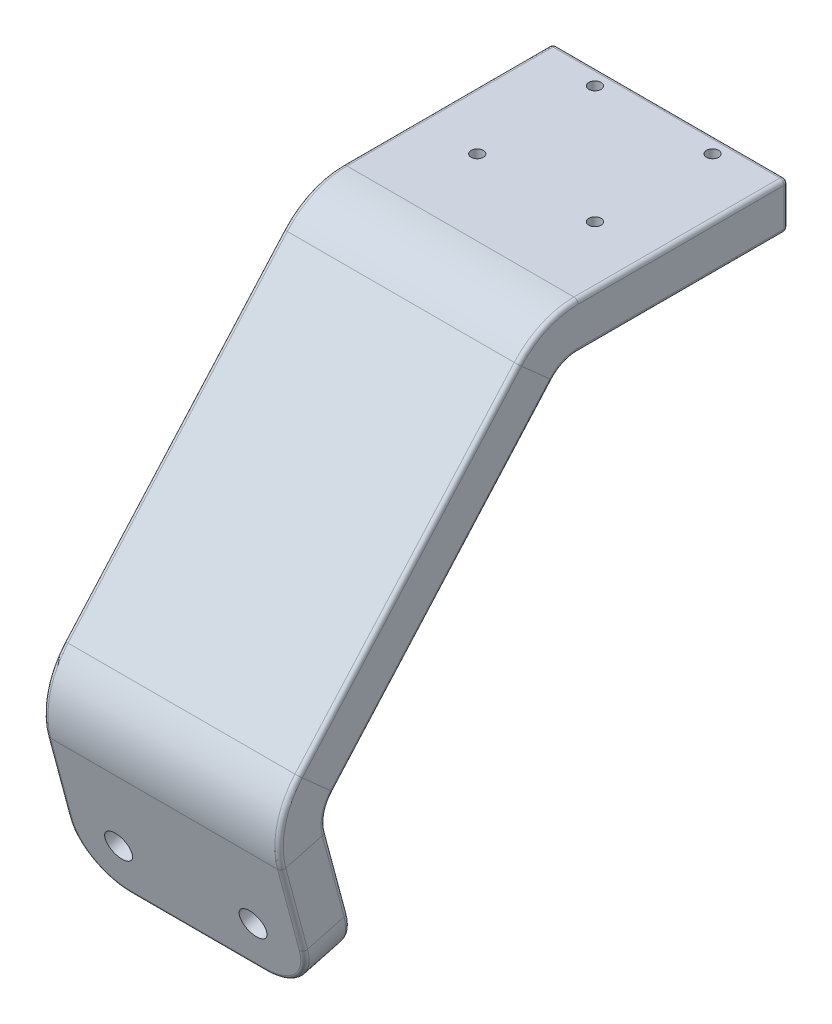
SolidWorks part; units mm, degrees
ref_plane "Front Plane" through (0, 0, 0) normal (0, 0, 1) x (1, 0, 0)
ref_plane "Top Plane" through (0, 0, 0) normal (0, 1, 0) x (1, 0, 0)
ref_plane "Right Plane" through (0, 0, 0) normal (1, 0, 0) x (0, 0, -1)
sketch "Sketch1" plane through (0, 0, 0) normal (0, 1, 0) x (1, 0, 0)
  line L0 (-12.7, 6.3002) -> (-12.7, 9.525) construction
  line L1 (-22.225, 9.525) -> (-22.225, -25.4)
  line L2 (-22.225, -25.4) -> (0, -25.4)
  line L3 (0, -25.4) -> (0, -12.7)
  line L4 (-17.4625, 14.2875) -> (-22.225, 14.2875)
  line L5 (-22.225, 14.2875) -> (-22.225, 9.525)
  line L6 (-17.4625, 14.2875) -> (0, 14.2875)
  line L7 (0, 14.2875) -> (0, -12.7)
  arc A0 (-12.7, 6.3002) -> (-7.1437, 0) centre (-6.35, 6.3002) ccw construction
  arc A2 (-12.7, 9.525) -> (-17.4625, 14.2875) centre (-17.4625, 9.525) ccw construction
  ellipse E0 centre (0, 0) end of major axis (0, 12.7) minor radius 7.1437 (0, -12.7) -> (-7.1437, 0) cw construction
  dimension "D5" = 6.35
  dimension "D7" = 4.7625
  dimension "D1" = 12.7
  dimension "D2" = 7.1437
  dimension "D3" = 12.7
  dimension "D6" = 9.525
  dimension "D8" = 12.7
extrude "Boss-Extrude1" add sketch "Sketch1" along normal mid plane 8.7312
mirror "Mirror1" about plane through (0, 4.3656, 25.4) normal (-1, 0, 0) of "Boss-Extrude1"
chamfer "Chamfer1" [suppressed] distance 5.08
fillet "Fillet1" [suppressed] radius 1.5875
sketch "Sketch2" plane through (0, 0, 0) normal (1, 0, 0) x (0, 0, -1)
  line L0 (-25.4, -4.3656) -> (-25.4, -10.7156) construction
  line L1 (-25.4, -10.7156) -> (-30.148, -6.4992) construction
  line L2 (-30.148, -6.4992) -> (-71.5574, -53.1291)
  line L3 (-72.943, -58.989) -> (-66.369, -83.5236)
  line L4 (14.2875, -4.3656) -> (-25.4, -4.3656) construction
  line L5 (-72.943, -58.989) -> (9.861, -36.8018) construction
  line L6 (9.861, -36.8018) -> (0, 0) construction
  arc A0 (-25.4, -4.3656) -> (-30.148, -6.4992) centre (-25.4, -10.7156) ccw
  arc A1 (-71.5574, -53.1291) -> (-72.943, -58.989) centre (-66.8094, -57.3455) ccw
  dimension "D1" = 6.35
  dimension "D2" = 75
  dimension "D3" = 25.4
  dimension "D4" = 85.725
  dimension "D5" = 38.1
sketch "Sketch3" plane through (0, 0, 25.4) normal (0, 0, 1) x (1, 0, 0)
  line L4 (-22.225, -4.3656) -> (22.225, -4.3656)
  line L5 (22.225, -4.3656) -> (22.225, 4.3656)
  line L6 (22.225, 4.3656) -> (-22.225, 4.3656)
  line L7 (-22.225, 4.3656) -> (-22.225, -4.3656)
  line L8 (-22.225, -4.3656) -> (22.225, -4.3656)
  line L9 (22.225, -4.3656) -> (22.225, 4.3656)
  line L10 (22.225, 4.3656) -> (-22.225, 4.3656)
  line L11 (-22.225, 4.3656) -> (-22.225, -4.3656)
  dimension "D1" = 0
sweep "Sweep1" add profiles "Sketch3" path "Sketch2"
fillet "Fillet3" radius 9.525 2 edges at (22.225, -84.6535, 70.5859) (-22.225, -84.6535, 70.5859)
fillet "Fillet2" radius 0.7937 30 edges at (-22.225, -66.6561, 70.8886) (-22.225, -55.8844, 72.989) (-22.225, -29.8141, 50.8527) (-22.225, -4.9235, 28.0027) (-22.225, -68.9159, 79.3223) (-22.225, -53.8753, 81.4859) (-22.225, -24.0165, 57.3813) (-22.225, 3.0406, 31.5814) (22.225, -66.6561, 70.8886) (22.225, -55.8844, 72.989) (22.225, -29.8141, 50.8527) (22.225, -4.9235, 28.0027) (22.225, -68.9159, 79.3223) (22.225, -53.8753, 81.4859) (22.225, -24.0165, 57.3813) (22.225, 3.0406, 31.5814) (-22.225, -4.3656, 5.5562) (-22.225, 4.3656, 5.5562) (22.225, -4.3656, 5.5562) (22.225, 4.3656, 5.5562) (-19.4352, -80.8288, 67.091) (0, -83.5236, 66.369) (19.4352, -80.8288, 67.091) (-19.4352, -83.0886, 75.5248) (0, -85.7834, 74.8027) (19.4352, -83.0886, 75.5248) (0, 4.3656, -14.2875) (22.225, 0, -14.2875) (-22.225, 0, -14.2875) (0, -4.3656, -14.2875)
hole_wizard "CSK for #10 Flat Head Machine Screw (100)1" positions "3DSketch1" profile "Sketch4" countersink size "#10" standard "ANSI Inch" end condition through all
sketch3d "3DSketch1"
  line L0 (-12.7, -75.2393, 72.2534) -> (-12.7, -73.1071, 64.296) construction
  line L1 (12.7, -75.2393, 72.2534) -> (12.7, -73.1071, 64.296) construction
  point P0 (-12.7, -74.3231, 68.8342)
  point P4 (12.7, -74.3231, 68.8342)
sketch "Sketch4" plane through (-12.7, -74.3231, 68.8342) normal (1, 0, 0) x (0, 0.9659, 0.2588)
  line L0 (0, 0) -> (0, 15.5315)
  line L1 (0, 15.5315) -> (2.5527, 15.5315)
  line L2 (2.5527, 15.5315) -> (2.5527, 1.9608)
  line L3 (2.5527, 1.9608) -> (4.8895, 0)
  line L5 (4.8895, 0) -> (0, 0)
  line L6 (-2.5527, 1.9608) -> (-4.8895, 0) construction
  line L11 (0, -6.35) -> (0, 107.95) construction
  dimension "Thru Hole Dia." = 5.1054
  dimension "Thru Hole Depth" = 15.5315
  dimension "Near C'Sink Dia." = 9.779
  dimension "Near C'Sink Angle" = 100
sketch "Sketch6" plane through (0, 4.3656, 0) normal (0, 1, 0) x (1, 0, 0)
  line L1 (-11.1125, -11.1125) -> (11.1125, -11.1125) construction
  line L2 (-11.1125, -11.1125) -> (-11.1125, 11.1125) construction
  line L3 (-11.1125, 11.1125) -> (11.1125, 11.1125) construction
  line L4 (11.1125, -11.1125) -> (11.1125, 11.1125) construction
  line L5 (-11.1125, -11.1125) -> (11.1125, 11.1125) construction
  line L6 (-11.1125, 11.1125) -> (11.1125, -11.1125) construction
  circle A0 centre (-11.1125, 11.1125) radius 1.15
  point P0 (0, 0)
  dimension "D2" = 2.3
  dimension "D1" = 22.225
ref_axis "Axis1" through (0, -90.1035, 0) along (0, 1, 0)
extrude "Cut-Extrude1" cut sketch "Sketch6" against normal through all
sketch "Sketch7" plane through (0, -4.3656, 0) normal (0, -1, 0) x (1, 0, 0)
  circle A0 centre (-11.1125, -11.1125) radius 1.905
  dimension "D1" = 3.81
extrude "Cut-Extrude2" cut sketch "Sketch7" against normal offset from surface (6.35 mm away) 2.3813 up to face at (-11.1125, 4.3656, -9.9625)
pattern_circular "CirPattern1" count 4 over 360 about axis through (0, -90.1035, 0) along (0, 1, 0) of "Cut-Extrude1", "Cut-Extrude2"
